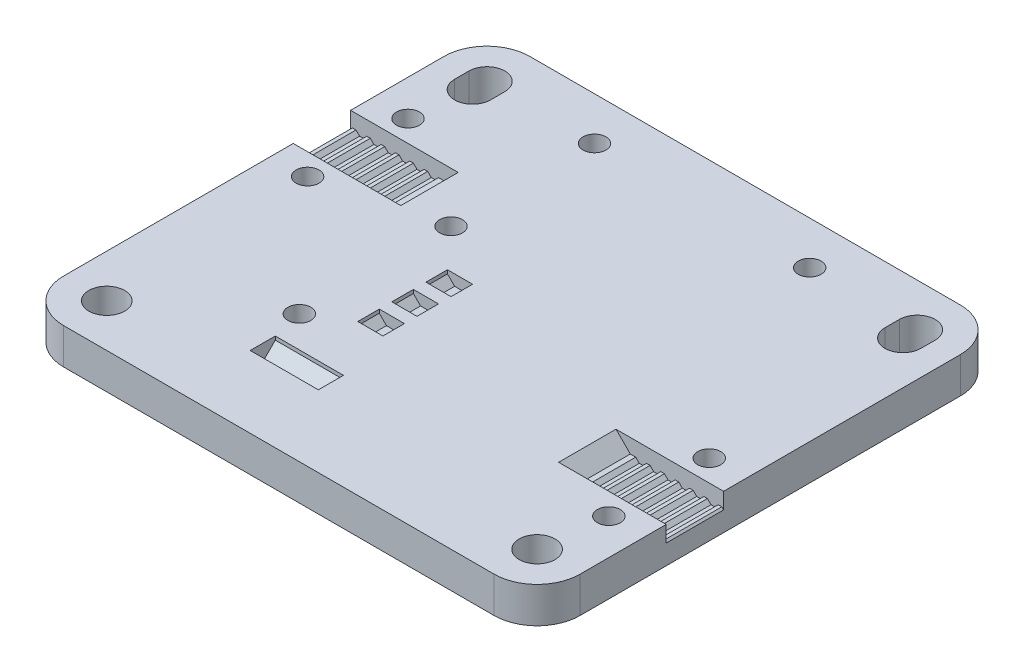
SolidWorks part; units mm, degrees
ref_plane "Front Plane" through (0, 0, 0) normal (0, 0, 1) x (1, 0, 0)
ref_plane "Top Plane" through (0, 0, 0) normal (0, 1, 0) x (1, 0, 0)
ref_plane "Right Plane" through (0, 0, 0) normal (1, 0, 0) x (0, 0, -1)
sketch "Sketch1" plane through (0, 0, 0) normal (0, 1, 0) x (1, 0, 0)
  line L0 (8.5, 59) -> (8.5, 57)
  line L1 (0, 0) -> (72, 0)
  line L2 (0, 0) -> (0, 65)
  line L3 (0, 65) -> (72, 65)
  line L4 (72, 0) -> (72, 65)
  line L5 (3.5, 59) -> (3.5, 57)
  line L6 (36, 65) -> (36, 0) construction
  line L7 (68.5, 59) -> (68.5, 57)
  line L8 (63.5, 59) -> (63.5, 57)
  arc A0 (8.5, 59) -> (3.5, 59) centre (6, 59) ccw
  arc A1 (3.5, 57) -> (8.5, 57) centre (6, 57) ccw
  circle A2 centre (6, 6) radius 2.5
  circle A3 centre (66, 6) radius 2.5
  arc A4 (68.5, 57) -> (63.5, 57) centre (66, 57) cw
  arc A5 (63.5, 59) -> (68.5, 59) centre (66, 59) cw
  circle A6 centre (5, 49) radius 1.6
  circle A7 centre (5, 35) radius 1.6
  circle A8 centre (21, 39) radius 1.6
  circle A9 centre (21, 59) radius 1.6
  circle A10 centre (51, 59) radius 1.6
  circle A11 centre (21, 17.85) radius 1.6
  circle A12 centre (67, 29) radius 1.6
  circle A13 centre (67, 15) radius 1.6
  point P39 (0, 0)
  point P40 (21, 39)
  point P41 (21, 39)
  point P42 (21, 59)
  point P43 (51, 59)
  dimension "D3" = 5
  dimension "D4" = 5
  dimension "D8" = 5
  dimension "D9" = 6
  dimension "D10" = 6
  dimension "D11" = 17.85
  dimension "D12" = 5
  dimension "D13" = 16
  dimension "D14" = 30
  dimension "D15" = 26
  dimension "D16" = 6
  dimension "D17" = 21
  dimension "D18" = 3.2
  dimension "D19" = 5
  dimension "D20" = 21
  dimension "D21" = 3.2
  dimension "D22" = 3.2
  dimension "D23" = 15
  dimension "D24" = 29
  dimension "D1" = 72
  dimension "D2" = 65
  dimension "D5" = 2
  dimension "D6" = 6
  dimension "D7" = 6
extrude "Boss-Extrude1" add sketch "Sketch1" along normal blind 5
fillet "Fillet1" radius 6 4 edges at (72, 2.5, 0) (72, 2.5, -65) (0, 2.5, -65) (0, 2.5, 0)
sketch "Sketch2" plane through (0, 5, 0) normal (0, 1, 0) x (1, 0, 0)
  line L0 (0, 59) -> (0, 6) construction
  line L1 (0, 46) -> (15, 46)
  line L2 (0, 46) -> (0, 38)
  line L3 (0, 38) -> (15, 38)
  line L4 (15, 46) -> (15, 38)
  line L5 (66, 65) -> (6, 65) construction
  line L6 (72, 6) -> (72, 59) construction
  line L7 (72, 18) -> (57, 18)
  line L8 (72, 18) -> (72, 26)
  line L9 (72, 26) -> (57, 26)
  line L10 (57, 18) -> (57, 26)
  line L11 (6, 0) -> (66, 0) construction
  line L13 (31.5, 13.5) -> (22, 13.5)
  line L14 (31.5, 13.5) -> (31.5, 10)
  line L15 (31.5, 10) -> (22, 10)
  line L16 (22, 13.5) -> (22, 10)
  dimension "D1" = 15
  dimension "D2" = 8
  dimension "D3" = 19
  dimension "D4" = 8
  dimension "D5" = 15
  dimension "D6" = 18
  dimension "D7" = 9.5
  dimension "D8" = 3.5
  dimension "D9" = 10
  dimension "D10" = 22
extrude "Cut-Extrude1" cut sketch "Sketch2" against normal blind 2
chamfer "Chamfer1" distance 2 angle 45 2 edges at (57, 3, -22) (15, 3, -42)
sketch "Sketch3" plane through (0, 3, 0) normal (0, 1, 0) x (1, 0, 0)
  line L1 (13, 46) -> (0, 46) construction
  line L2 (1.25, 46) -> (1.75, 46)
  line L3 (1.25, 46) -> (1.25, 38)
  line L4 (1.25, 38) -> (1.75, 38)
  line L8 (1.75, 46) -> (1.75, 38)
  line L9 (0, 38) -> (15, 38) construction
  line L10 (15, 46) -> (0, 46) construction
  line L11 (3.25, 46) -> (3.75, 46)
  line L13 (3.25, 46) -> (3.25, 38)
  line L14 (3.25, 38) -> (3.75, 38)
  line L15 (3.75, 46) -> (3.75, 38)
  line L16 (5.25, 46) -> (5.75, 46)
  line L18 (5.25, 46) -> (5.25, 38)
  line L19 (5.25, 38) -> (5.75, 38)
  line L20 (5.75, 46) -> (5.75, 38)
  line L21 (0, 38) -> (13, 38) construction
  line L23 (11.25, 46) -> (11.75, 46)
  line L24 (11.25, 46) -> (11.25, 38)
  line L25 (11.25, 38) -> (11.75, 38)
  line L26 (7.25, 46) -> (7.75, 46)
  line L27 (7.25, 46) -> (7.25, 38)
  line L28 (7.25, 38) -> (7.75, 38)
  line L29 (7.75, 46) -> (7.75, 38)
  line L30 (0, 46) -> (0, 38) construction
  line L31 (9.25, 46) -> (9.75, 46)
  line L32 (9.25, 46) -> (9.25, 38)
  line L33 (9.25, 38) -> (9.75, 38)
  line L35 (72, 26) -> (59, 26) construction
  line L36 (70.75, 26) -> (70.25, 26)
  line L37 (70.75, 26) -> (70.75, 18)
  line L38 (70.75, 18) -> (70.25, 18)
  line L41 (70.25, 26) -> (70.25, 18)
  line L42 (57, 18) -> (72, 18) construction
  line L43 (72, 18) -> (72, 26) construction
  line L44 (68.75, 26) -> (68.25, 26)
  line L46 (68.75, 26) -> (68.75, 18)
  line L47 (68.75, 18) -> (68.25, 18)
  line L48 (68.25, 26) -> (68.25, 18)
  line L49 (66.75, 26) -> (66.25, 26)
  line L50 (66.75, 26) -> (66.75, 18)
  line L51 (66.75, 18) -> (66.25, 18)
  line L52 (66.25, 26) -> (66.25, 18)
  line L53 (64.75, 26) -> (64.25, 26)
  line L54 (64.75, 26) -> (64.75, 18)
  line L55 (64.75, 18) -> (64.25, 18)
  line L56 (64.25, 26) -> (64.25, 18)
  line L57 (62.75, 26) -> (62.25, 26)
  line L59 (62.75, 26) -> (62.75, 18)
  line L60 (62.75, 18) -> (62.25, 18)
  line L61 (62.25, 26) -> (62.25, 18)
  line L62 (60.75, 26) -> (60.25, 26)
  line L63 (60.75, 26) -> (60.75, 18)
  line L64 (60.75, 18) -> (60.25, 18)
  line L65 (60.25, 26) -> (60.25, 18)
  line L67 (9.75, 46) -> (9.75, 38)
  line L68 (11.75, 46) -> (11.75, 38)
  dimension "D3" = 1.25
  dimension "D4" = 0.5
  dimension "D5" = 1.5
  dimension "D6" = 0.5
  dimension "D7" = 1.5
  dimension "D8" = 0.5
  dimension "D9" = 1.5
  dimension "D10" = 0.5
  dimension "D11" = 0.5
  dimension "D12" = 1.5
  dimension "D13" = 1.5
  dimension "D14" = 0.5
  dimension "D15" = 1.25
  dimension "D16" = 0.5
  dimension "D17" = 1.5
  dimension "D18" = 0.5
  dimension "D19" = 1.5
  dimension "D20" = 0.5
  dimension "D21" = 1.5
  dimension "D22" = 0.5
  dimension "D23" = 1.5
  dimension "D24" = 0.5
  dimension "D25" = 1.5
  dimension "D26" = 0.5
extrude "Cut-Extrude2" cut sketch "Sketch3" against normal blind 0.5
chamfer "Chamfer2" distance 0.5 angle 45 24 edges at (70.75, 3, -22) (70.25, 3, -22) (68.75, 3, -22) (68.25, 3, -22) (66.75, 3, -22) (66.25, 3, -22) (64.75, 3, -22) (64.25, 3, -22) (62.75, 3, -22) (62.25, 3, -22) (60.75, 3, -22) (60.25, 3, -22) (11.75, 3, -42) (11.25, 3, -42) (9.75, 3, -42) (9.25, 3, -42) (7.75, 3, -42) (7.25, 3, -42) (5.75, 3, -42) (5.25, 3, -42) (3.75, 3, -42) (3.25, 3, -42) (1.75, 3, -42) (1.25, 3, -42)
chamfer "Chamfer3" distance 0.25 angle 45 2 edges at (72, 3, -22) (0, 3, -42)
sketch "Sketch4" plane through (0, 0, 0) normal (0, -1, 0) x (1, 0, 0)
  line L1 (8.4064, -49) -> (6.7032, -46.05)
  line L2 (6.7032, -46.05) -> (3.2968, -46.05)
  line L3 (3.2968, -46.05) -> (1.5936, -49)
  line L4 (1.5936, -49) -> (3.2968, -51.95)
  line L5 (3.2968, -51.95) -> (6.7032, -51.95)
  line L6 (6.7032, -51.95) -> (8.4064, -49)
  line L7 (8.4064, -35) -> (6.7032, -32.05)
  line L8 (6.7032, -32.05) -> (3.2968, -32.05)
  line L9 (3.2968, -32.05) -> (1.5936, -35)
  line L10 (1.5936, -35) -> (3.2968, -37.95)
  line L11 (3.2968, -37.95) -> (6.7032, -37.95)
  line L12 (6.7032, -37.95) -> (8.4064, -35)
  line L13 (24.4064, -39) -> (22.7032, -36.05)
  line L14 (22.7032, -36.05) -> (19.2968, -36.05)
  line L15 (19.2968, -36.05) -> (17.5936, -39)
  line L16 (17.5936, -39) -> (19.2968, -41.95)
  line L17 (19.2968, -41.95) -> (22.7032, -41.95)
  line L18 (22.7032, -41.95) -> (24.4064, -39)
  line L19 (24.4064, -17.85) -> (22.7032, -14.9)
  line L20 (22.7032, -14.9) -> (19.2968, -14.9)
  line L21 (19.2968, -14.9) -> (17.5936, -17.85)
  line L22 (17.5936, -17.85) -> (19.2968, -20.8)
  line L23 (19.2968, -20.8) -> (22.7032, -20.8)
  line L24 (22.7032, -20.8) -> (24.4064, -17.85)
  line L25 (54.4064, -59) -> (52.7032, -56.05)
  line L26 (52.7032, -56.05) -> (49.2968, -56.05)
  line L27 (49.2968, -56.05) -> (47.5936, -59)
  line L28 (47.5936, -59) -> (49.2968, -61.95)
  line L29 (49.2968, -61.95) -> (52.7032, -61.95)
  line L30 (52.7032, -61.95) -> (54.4064, -59)
  line L31 (24.4064, -59) -> (22.7032, -56.05)
  line L32 (22.7032, -56.05) -> (19.2968, -56.05)
  line L33 (19.2968, -56.05) -> (17.5936, -59)
  line L34 (17.5936, -59) -> (19.2968, -61.95)
  line L35 (19.2968, -61.95) -> (22.7032, -61.95)
  line L36 (22.7032, -61.95) -> (24.4064, -59)
  line L49 (70.4064, -15) -> (68.7032, -12.05)
  line L50 (68.7032, -12.05) -> (65.2968, -12.05)
  line L51 (65.2968, -12.05) -> (63.5936, -15)
  line L52 (63.5936, -15) -> (65.2968, -17.95)
  line L53 (65.2968, -17.95) -> (68.7032, -17.95)
  line L54 (68.7032, -17.95) -> (70.4064, -15)
  line L55 (70.4064, -29) -> (68.7032, -26.05)
  line L56 (68.7032, -26.05) -> (65.2968, -26.05)
  line L57 (65.2968, -26.05) -> (63.5936, -29)
  line L58 (63.5936, -29) -> (65.2968, -31.95)
  line L59 (65.2968, -31.95) -> (68.7032, -31.95)
  line L60 (68.7032, -31.95) -> (70.4064, -29)
  circle A0 centre (5, -49) radius 2.95 construction
  circle A1 centre (5, -35) radius 2.95 construction
  circle A2 centre (21, -39) radius 2.95 construction
  circle A3 centre (21, -17.85) radius 2.95 construction
  circle A4 centre (51, -59) radius 2.95 construction
  circle A5 centre (21, -59) radius 2.95 construction
  circle A8 centre (67, -15) radius 2.95 construction
  circle A9 centre (67, -29) radius 2.95 construction
  point P46 (51, -39)
  point P55 (0, 0)
  point P56 (21, -17.85)
  dimension "D1" = 5.9
  dimension "D2" = 5.9
  dimension "D3" = 5.9
  dimension "D4" = 5.9
  dimension "D5" = 5.9
  dimension "D6" = 5.9
  dimension "D7" = 5.9
  dimension "D8" = 5.9
extrude "Cut-Extrude3" cut sketch "Sketch4" against normal blind 2.5
sketch "Sketch5" plane through (0, 5, 0) normal (0, 1, 0) x (1, 0, 0)
  line L0 (6, 0) -> (66, 0) construction
  line L1 (26, 33.5) -> (29.5, 33.5)
  line L2 (26, 33.5) -> (26, 30.5)
  line L3 (26, 30.5) -> (29.5, 30.5)
  line L4 (29.5, 33.5) -> (29.5, 30.5)
  line L5 (26, 28.75) -> (29.5, 28.75)
  line L6 (26, 28.75) -> (26, 25.75)
  line L7 (26, 25.75) -> (29.5, 25.75)
  line L8 (29.5, 28.75) -> (29.5, 25.75)
  line L9 (26, 24) -> (29.5, 24)
  line L10 (26, 24) -> (26, 21)
  line L11 (26, 21) -> (29.5, 21)
  line L12 (29.5, 24) -> (29.5, 21)
  line L13 (0, 38) -> (0, 6) construction
  point P16 (0, 0)
  point P17 (0, 0)
  point P18 (0, 0)
  dimension "D1" = 3.5
  dimension "D2" = 3
  dimension "D3" = 21
  dimension "D4" = 26
  dimension "D5" = 1.75
  dimension "D6" = 1.75
  dimension "D7" = 3
  dimension "D8" = 3
extrude "Cut-Extrude4" cut sketch "Sketch5" against normal blind 1.5
chamfer "Chamfer4" distance 1.5 angle 45 2 edges at (26.75, 3, -10) (26.75, 3, -13.5)
chamfer "Chamfer5" distance 1 angle 45 6 edges at (29.5, 3.5, -22.5) (29.5, 3.5, -27.25) (29.5, 3.5, -32) (26, 3.5, -32) (26, 3.5, -27.25) (26, 3.5, -22.5)
